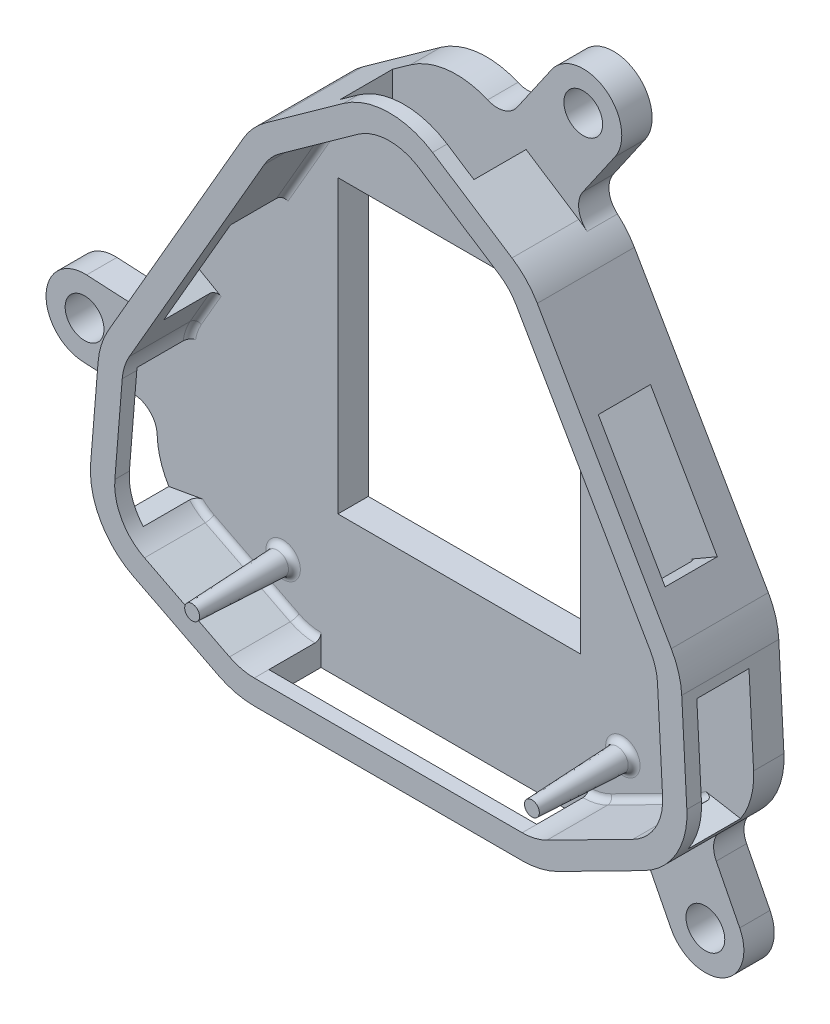
SolidWorks part; units mm, degrees
ref_plane "Front" through (0, 0, 0) normal (0, 0, 1) x (1, 0, 0)
ref_plane "Top" through (0, 0, 0) normal (0, 1, 0) x (1, 0, 0)
ref_plane "Right" through (0, 0, 0) normal (1, 0, 0) x (0, 0, -1)
sketch "Model" plane through (0, 0, 0) normal (0, 0, 1) x (1, 0, 0)
  line L0 (36.2734, 12.0044) -> (37.9734, 12.0044)
  line L1 (37.9734, 12.0044) -> (37.9734, 10.3044)
  line L2 (37.9734, 10.3044) -> (36.2734, 10.3044)
  line L3 (36.2734, 10.3044) -> (36.2734, 12.0044)
  line L4 (21.2021, 39.0514) -> (32.2167, 39.0514)
  line L5 (21.2021, 31.2458) -> (21.2021, 39.0514)
  line L6 (21.2021, 31.2458) -> (32.2167, 31.2458)
  line L7 (32.2167, 31.2458) -> (32.2167, 39.0514)
  line L8 (21.2021, 31.2458) -> (21.2021, 39.0514)
  line L9 (21.2021, 39.0514) -> (32.2167, 39.0514)
  line L10 (32.2167, 39.0514) -> (32.2167, 31.2458)
  line L11 (32.2167, 31.2458) -> (21.2021, 31.2458)
  line L12 (38.8861, 6.1621) -> (46.5731, 4.8066)
  line L13 (38.8861, 6.1621) -> (40.7988, 17.0093)
  line L14 (40.7988, 17.0093) -> (48.4858, 15.6539)
  line L15 (46.5731, 4.8066) -> (48.4858, 15.6539)
  line L16 (40.7988, 17.0093) -> (48.4858, 15.6539)
  line L17 (48.4858, 15.6539) -> (46.5731, 4.8066)
  line L18 (46.5731, 4.8066) -> (38.8861, 6.1621)
  line L19 (38.8861, 6.1621) -> (40.7988, 17.0093)
  line L20 (39.5023, 17.0656) -> (46.2621, 20.9684)
  line L21 (33.995, 26.6045) -> (39.5023, 17.0656)
  line L22 (33.995, 26.6045) -> (40.7548, 30.5073)
  line L23 (40.7548, 30.5073) -> (46.2621, 20.9684)
  line L24 (33.995, 26.6045) -> (40.7548, 30.5073)
  line L25 (40.7548, 30.5073) -> (46.2621, 20.9684)
  line L26 (46.2621, 20.9684) -> (39.5023, 17.0656)
  line L27 (39.5023, 17.0656) -> (33.995, 26.6045)
  line L28 (15.1061, 0.2754) -> (26.1207, 0.2754)
  line L29 (26.1207, 0.2754) -> (26.1207, 8.081)
  line L30 (15.1061, 8.081) -> (26.1207, 8.081)
  line L31 (15.1061, 0.2754) -> (15.1061, 8.081)
  line L32 (26.1207, 8.081) -> (26.1207, 0.2754)
  line L33 (26.1207, 0.2754) -> (15.1061, 0.2754)
  line L34 (15.1061, 0.2754) -> (15.1061, 8.081)
  line L35 (15.1061, 8.081) -> (26.1207, 8.081)
  line L36 (4.3045, 15.8277) -> (11.9916, 17.1831)
  line L37 (11.9916, 17.1831) -> (13.9042, 6.3359)
  line L38 (6.2172, 4.9804) -> (13.9042, 6.3359)
  line L39 (4.3045, 15.8277) -> (6.2172, 4.9804)
  line L40 (13.9042, 6.3359) -> (6.2172, 4.9804)
  line L41 (6.2172, 4.9804) -> (4.3045, 15.8277)
  line L42 (4.3045, 15.8277) -> (11.9916, 17.1831)
  line L43 (11.9916, 17.1831) -> (13.9042, 6.3359)
  line L44 (26.5601, 0.2754) -> (37.5747, 0.2754)
  line L45 (37.5747, 0.2754) -> (37.5747, 8.081)
  line L46 (26.5601, 8.081) -> (37.5747, 8.081)
  line L47 (26.5601, 0.2754) -> (26.5601, 8.081)
  line L48 (37.5747, 8.081) -> (37.5747, 0.2754)
  line L49 (37.5747, 0.2754) -> (26.5601, 0.2754)
  line L50 (26.5601, 0.2754) -> (26.5601, 8.081)
  line L51 (26.5601, 8.081) -> (37.5747, 8.081)
  line L52 (12.156, 29.8723) -> (18.9159, 25.9695)
  line L53 (13.4086, 16.4306) -> (18.9159, 25.9695)
  line L54 (6.6488, 20.3334) -> (13.4086, 16.4306)
  line L55 (6.6488, 20.3334) -> (12.156, 29.8723)
  line L56 (13.4086, 16.4306) -> (6.6487, 20.3334)
  line L57 (6.6487, 20.3334) -> (12.156, 29.8723)
  line L58 (12.156, 29.8723) -> (18.9159, 25.9695)
  line L59 (18.9159, 25.9695) -> (13.4086, 16.4306)
  line L60 (26.6632, 0.1484) -> (37.6778, 0.1484)
  line L61 (26.6632, 0.1484) -> (26.6632, 7.954)
  line L62 (26.6632, 7.954) -> (37.6778, 7.954)
  line L63 (37.6778, 0.1484) -> (37.6778, 7.954)
  line L64 (26.6632, 7.954) -> (26.6632, 0.1484)
  line L65 (26.6632, 0.1484) -> (37.6778, 0.1484)
  line L66 (37.6778, 0.1484) -> (37.6778, 7.954)
  line L67 (37.6778, 7.954) -> (26.6632, 7.954)
  line L68 (26.1207, 0.1483) -> (26.1207, 7.954)
  line L69 (15.1062, 7.954) -> (26.1207, 7.954)
  line L70 (15.1062, 0.1483) -> (15.1062, 7.954)
  line L71 (15.1062, 0.1483) -> (26.1207, 0.1483)
  line L72 (15.1061, 7.954) -> (15.1061, 0.1484)
  line L73 (15.1061, 0.1484) -> (26.1207, 0.1484)
  line L74 (26.1207, 0.1484) -> (26.1207, 7.954)
  line L75 (26.1207, 7.954) -> (15.1061, 7.954)
  line L76 (33.0594, 32.3634) -> (33.0594, 33.8874)
  line L77 (33.0594, 33.8874) -> (34.5834, 33.8874)
  line L78 (34.5834, 33.8874) -> (34.5834, 32.3634)
  line L79 (34.5834, 32.3634) -> (33.0594, 32.3634)
  line L80 (18.2094, 12.0434) -> (18.2094, 13.5674)
  line L81 (18.2094, 13.5674) -> (19.7334, 13.5674)
  line L82 (19.7334, 13.5674) -> (19.7334, 12.0434)
  line L83 (19.7334, 12.0434) -> (18.2094, 12.0434)
  line L84 (6.4942, 4.2177) -> (13.4987, 0.6545)
  line L85 (5.453, 17.2714) -> (16.5709, 36.5281)
  line L86 (4.321, 8.1074) -> (4.9303, 15.5958)
  line L87 (17.7062, 37.7804) -> (24.1332, 42.3823)
  line L88 (15.3123, 0.2198) -> (37.3945, 0.2198)
  line L89 (28.6426, 42.4833) -> (35.1901, 38.2252)
  line L90 (39.2081, 0.6545) -> (46.2848, 4.2545)
  line L91 (48.0448, 15.9602) -> (48.4656, 8.0316)
  line L92 (36.4735, 36.8719) -> (47.5146, 17.7482)
  circle A0 centre (26.7094, 25.3784) radius 1.4
  circle A1 centre (26.7094, 17.3784) radius 1.4
  circle A2 centre (37.1234, 18.7744) radius 0.85
  circle A3 centre (37.1234, 16.2344) radius 0.85
  circle A4 centre (37.1234, 13.6944) radius 0.85
  circle A5 centre (37.1234, 8.6144) radius 0.85
  circle A6 centre (21.2021, 39.0514) radius 0.0381
  circle A7 centre (32.2167, 39.0514) radius 0.0381
  circle A8 centre (21.2021, 31.2458) radius 0.0381
  circle A9 centre (21.2021, 39.0514) radius 0.0381
  circle A10 centre (21.2021, 31.2458) radius 0.0381
  circle A11 centre (32.2167, 31.2458) radius 0.0381
  circle A12 centre (32.2167, 31.2458) radius 0.0381
  circle A13 centre (32.2167, 39.0514) radius 0.0381
  circle A14 centre (38.8861, 6.1621) radius 0.0381
  circle A15 centre (46.5731, 4.8066) radius 0.0381
  circle A16 centre (38.8861, 6.1621) radius 0.0381
  circle A17 centre (40.7988, 17.0093) radius 0.0381
  circle A18 centre (40.7988, 17.0093) radius 0.0381
  circle A19 centre (48.4858, 15.6539) radius 0.0381
  circle A20 centre (46.5731, 4.8066) radius 0.0381
  circle A21 centre (48.4858, 15.6539) radius 0.0381
  circle A22 centre (39.5023, 17.0656) radius 0.0381
  circle A23 centre (46.2621, 20.9684) radius 0.0381
  circle A24 centre (33.995, 26.6045) radius 0.0381
  circle A25 centre (39.5023, 17.0656) radius 0.0381
  circle A26 centre (33.995, 26.6045) radius 0.0381
  circle A27 centre (40.7548, 30.5073) radius 0.0381
  circle A28 centre (40.7548, 30.5073) radius 0.0381
  circle A29 centre (46.2621, 20.9684) radius 0.0381
  circle A30 centre (15.1061, 0.2754) radius 0.0381
  circle A31 centre (26.1207, 0.2754) radius 0.0381
  circle A32 centre (26.1207, 0.2754) radius 0.0381
  circle A33 centre (26.1207, 8.081) radius 0.0381
  circle A34 centre (15.1061, 8.081) radius 0.0381
  circle A35 centre (26.1207, 8.081) radius 0.0381
  circle A36 centre (15.1061, 0.2754) radius 0.0381
  circle A37 centre (15.1061, 8.081) radius 0.0381
  circle A38 centre (4.3045, 15.8277) radius 0.0381
  circle A39 centre (11.9916, 17.1831) radius 0.0381
  circle A40 centre (11.9916, 17.1831) radius 0.0381
  circle A41 centre (13.9042, 6.3359) radius 0.0381
  circle A42 centre (6.2172, 4.9804) radius 0.0381
  circle A43 centre (13.9042, 6.3359) radius 0.0381
  circle A44 centre (4.3045, 15.8277) radius 0.0381
  circle A45 centre (6.2172, 4.9804) radius 0.0381
  circle A46 centre (26.5601, 0.2754) radius 0.0381
  circle A47 centre (37.5747, 0.2754) radius 0.0381
  circle A48 centre (37.5747, 0.2754) radius 0.0381
  circle A49 centre (37.5747, 8.081) radius 0.0381
  circle A50 centre (26.5601, 8.081) radius 0.0381
  circle A51 centre (37.5747, 8.081) radius 0.0381
  circle A52 centre (26.5601, 0.2754) radius 0.0381
  circle A53 centre (26.5601, 8.081) radius 0.0381
  circle A54 centre (12.156, 29.8723) radius 0.0381
  circle A55 centre (18.9159, 25.9695) radius 0.0381
  circle A56 centre (13.4086, 16.4306) radius 0.0381
  circle A57 centre (18.9159, 25.9695) radius 0.0381
  circle A58 centre (6.6488, 20.3334) radius 0.0381
  circle A59 centre (13.4086, 16.4306) radius 0.0381
  circle A60 centre (6.6488, 20.3334) radius 0.0381
  circle A61 centre (12.156, 29.8723) radius 0.0381
  circle A62 centre (26.6632, 0.1484) radius 0.0381
  circle A63 centre (37.6778, 0.1484) radius 0.0381
  circle A64 centre (26.6632, 0.1484) radius 0.0381
  circle A65 centre (26.6632, 7.954) radius 0.0381
  circle A66 centre (26.6632, 7.954) radius 0.0381
  circle A67 centre (37.6778, 7.954) radius 0.0381
  circle A68 centre (37.6778, 0.1484) radius 0.0381
  circle A69 centre (37.6778, 7.954) radius 0.0381
  circle A70 centre (26.1207, 0.1483) radius 0.0381
  circle A71 centre (26.1207, 7.954) radius 0.0381
  circle A72 centre (15.1062, 7.954) radius 0.0381
  circle A73 centre (26.1207, 7.954) radius 0.0381
  circle A74 centre (15.1062, 0.1483) radius 0.0381
  circle A75 centre (15.1062, 7.954) radius 0.0381
  circle A76 centre (15.1062, 0.1483) radius 0.0381
  circle A77 centre (26.1207, 0.1483) radius 0.0381
  circle A78 centre (18.9714, 22.9654) radius 0.762
  circle A79 centre (18.9714, 25.5054) radius 0.762
  circle A80 centre (18.9714, 28.0454) radius 0.762
  circle A81 centre (18.9714, 30.5854) radius 0.762
  circle A82 centre (18.9714, 33.1254) radius 0.762
  circle A83 centre (33.8214, 10.2654) radius 0.762
  circle A84 centre (33.8214, 12.8054) radius 0.762
  circle A85 centre (33.8214, 15.3454) radius 0.762
  circle A86 centre (33.8214, 17.8854) radius 0.762
  circle A87 centre (33.8214, 20.4254) radius 0.762
  circle A88 centre (33.8214, 22.9654) radius 0.762
  circle A89 centre (33.8214, 25.5054) radius 0.762
  circle A90 centre (33.8214, 28.0454) radius 0.762
  circle A91 centre (33.8214, 30.5854) radius 0.762
  circle A92 centre (18.9714, 20.4254) radius 0.762
  circle A93 centre (18.9714, 17.8854) radius 0.762
  circle A94 centre (18.9714, 15.3454) radius 0.762
  circle A95 centre (18.9714, 10.2654) radius 0.762
  circle A96 centre (6.4942, 4.2177) radius 0.0032
  circle A97 centre (13.4987, 0.6545) radius 0.0032
  circle A98 centre (5.453, 17.2714) radius 0.0032
  circle A99 centre (16.5709, 36.5281) radius 0.0032
  circle A100 centre (4.321, 8.1074) radius 0.0032
  circle A101 centre (4.9303, 15.5958) radius 0.0032
  circle A102 centre (17.7062, 37.7804) radius 0.0032
  circle A103 centre (24.1332, 42.3823) radius 0.0032
  circle A104 centre (15.3123, 0.2198) radius 0.0032
  circle A105 centre (37.3945, 0.2198) radius 0.0032
  circle A106 centre (28.6426, 42.4833) radius 0.0032
  circle A107 centre (35.1901, 38.2252) radius 0.0032
  circle A108 centre (39.2081, 0.6545) radius 0.0032
  circle A109 centre (46.2848, 4.2545) radius 0.0032
  circle A110 centre (48.0448, 15.9602) radius 0.0032
  circle A111 centre (48.4656, 8.0316) radius 0.0032
  circle A112 centre (36.4735, 36.8719) radius 0.0032
  circle A113 centre (47.5146, 17.7482) radius 0.0032
  arc A114 (4.321, 8.1074) -> (6.4942, 4.2177) centre (8.3078, 7.783) ccw
  circle A115 centre (6.4942, 4.2177) radius 0.0032
  circle A116 centre (4.321, 8.1074) radius 0.0032
  arc A117 (28.6426, 42.4833) -> (24.1332, 42.3823) centre (26.4619, 39.13) ccw
  circle A118 centre (24.1332, 42.3823) radius 0.0032
  circle A119 centre (28.6426, 42.4833) radius 0.0032
  arc A120 (5.453, 17.2714) -> (4.9303, 15.5958) centre (8.9171, 15.2714) ccw
  circle A121 centre (4.9303, 15.5958) radius 0.0032
  circle A122 centre (5.453, 17.2714) radius 0.0032
  arc A123 (17.7062, 37.7804) -> (16.5709, 36.5281) centre (20.035, 34.5282) ccw
  circle A124 centre (16.5709, 36.5281) radius 0.0032
  circle A125 centre (17.7063, 37.7804) radius 0.0032
  arc A126 (36.4735, 36.8719) -> (35.1901, 38.2252) centre (33.0094, 34.8719) ccw
  circle A127 centre (35.1901, 38.2252) radius 0.0032
  circle A128 centre (36.4735, 36.8719) radius 0.0032
  arc A129 (37.3945, 0.2198) -> (39.2081, 0.6545) centre (37.3946, 4.2198) ccw
  circle A130 centre (39.2081, 0.6545) radius 0.0032
  circle A131 centre (37.3945, 0.2197) radius 0.0032
  arc A132 (46.2848, 4.2545) -> (48.4656, 8.0316) centre (44.4712, 7.8197) ccw
  circle A133 centre (48.4656, 8.0316) radius 0.0032
  circle A134 centre (46.2848, 4.2544) radius 0.0032
  arc A135 (48.0448, 15.9602) -> (47.5146, 17.7482) centre (44.0504, 15.7483) ccw
  circle A136 centre (47.5146, 17.7482) radius 0.0032
  circle A137 centre (48.0448, 15.9602) radius 0.0032
  arc A138 (13.4987, 0.6545) -> (15.3123, 0.2198) centre (15.3123, 4.2198) ccw
  circle A139 centre (15.3124, 0.2197) radius 0.0032
  circle A140 centre (13.4987, 0.6545) radius 0.0032
  circle A141 centre (40.1914, 3.8534) radius 1.5
  circle A142 centre (26.4554, 40.8724) radius 1.5
  circle A143 centre (12.1915, 3.8534) radius 1.5
sketch "Sketch4" plane through (0, 0, 0) normal (0, 0, 1) x (1, 0, 0)
  line L0 (26.7094, 25.3784) -> (26.7094, 17.3784) construction
  line L1 (36.7094, 9.3784) -> (16.7094, 9.3784)
  line L2 (36.7094, 9.3784) -> (36.7094, 33.3784)
  line L3 (36.7094, 33.3784) -> (16.7094, 33.3784)
  line L4 (16.7094, 9.3784) -> (16.7094, 33.3784)
  line L5 (36.7094, 9.3784) -> (16.7094, 33.3784) construction
  line L6 (36.7094, 33.3784) -> (16.7094, 9.3784) construction
  line L89 (14.4058, 37.7781) -> (3.2879, 18.5214)
  line L90 (2.4385, 15.7986) -> (1.8292, 8.3101)
  line L91 (5.3607, 1.9895) -> (12.3653, -1.5738)
  line L92 (15.3124, -2.2802) -> (37.3945, -2.2802)
  line L93 (40.3416, -1.5738) -> (47.4183, 2.0262)
  line L94 (50.9621, 8.1641) -> (50.5413, 16.0927)
  line L95 (49.6796, 18.9982) -> (38.6386, 38.1219)
  line L96 (36.5531, 40.321) -> (30.0056, 44.5791)
  line L97 (22.6777, 44.4149) -> (16.2508, 39.8131)
  line L98 (16.1379, 36.7781) -> (5.02, 17.5214)
  line L99 (4.4319, 15.6364) -> (3.8226, 8.1479)
  line L100 (6.2675, 3.7721) -> (13.272, 0.2089)
  line L101 (15.3124, -0.2802) -> (37.3945, -0.2802)
  line L102 (39.4348, 0.2089) -> (46.5115, 3.8088)
  line L103 (48.9649, 8.0581) -> (48.5441, 15.9867)
  line L104 (47.9476, 17.9982) -> (36.9065, 37.1219)
  line L105 (35.4627, 38.6443) -> (28.9152, 42.9024)
  line L106 (23.8421, 42.7888) -> (17.4152, 38.1869)
  line L107 (16.1379, 36.7781) -> (5.02, 17.5214)
  line L108 (4.4319, 15.6364) -> (3.8226, 8.1479)
  line L109 (6.2675, 3.7721) -> (13.272, 0.2089)
  line L110 (15.3124, -0.2802) -> (37.3945, -0.2802)
  line L111 (39.4348, 0.2089) -> (46.5115, 3.8088)
  line L112 (48.9649, 8.0581) -> (48.5441, 15.9867)
  line L113 (47.9476, 17.9982) -> (36.9065, 37.1219)
  line L114 (35.4627, 38.6443) -> (28.9152, 42.9024)
  line L115 (23.8421, 42.7888) -> (17.4152, 38.1869)
  circle A5 centre (12.1915, 3.8534) radius 1.05
  circle A6 centre (12.1915, 3.8534) radius 1.05
  circle A7 centre (26.3789, 18.2477) radius 27.3825 construction
  circle A8 centre (40.1914, 3.8534) radius 1.05
  circle A9 centre (40.1914, 3.8534) radius 1.05
  arc A81 (3.2879, 18.5214) -> (2.4385, 15.7986) centre (8.9171, 15.2714) ccw
  arc A82 (1.8292, 8.3101) -> (5.3607, 1.9895) centre (8.3078, 7.783) ccw
  arc A83 (12.3653, -1.5738) -> (15.3124, -2.2802) centre (15.3123, 4.2198) ccw
  arc A84 (37.3945, -2.2802) -> (40.3416, -1.5738) centre (37.3946, 4.2198) ccw
  arc A85 (47.4183, 2.0262) -> (50.9621, 8.1641) centre (44.4712, 7.8197) ccw
  arc A86 (50.5413, 16.0927) -> (49.6796, 18.9982) centre (44.0504, 15.7483) ccw
  arc A87 (38.6386, 38.1219) -> (36.5531, 40.321) centre (33.0094, 34.8719) ccw
  arc A88 (30.0056, 44.5791) -> (22.6777, 44.4149) centre (26.4619, 39.13) ccw
  arc A89 (16.2508, 39.8131) -> (14.4058, 37.7781) centre (20.035, 34.5282) ccw
  arc A90 (17.4152, 38.1869) -> (16.1379, 36.7781) centre (20.035, 34.5282) ccw
  arc A91 (5.02, 17.5214) -> (4.4319, 15.6364) centre (8.9171, 15.2714) ccw
  arc A92 (3.8226, 8.1479) -> (6.2675, 3.7721) centre (8.3078, 7.783) ccw
  arc A93 (13.272, 0.2089) -> (15.3124, -0.2802) centre (15.3123, 4.2198) ccw
  arc A94 (37.3945, -0.2802) -> (39.4348, 0.2089) centre (37.3946, 4.2198) ccw
  arc A95 (46.5115, 3.8088) -> (48.9649, 8.0581) centre (44.4712, 7.8197) ccw
  arc A96 (48.5441, 15.9867) -> (47.9476, 17.9982) centre (44.0504, 15.7483) ccw
  arc A97 (36.9065, 37.1219) -> (35.4627, 38.6443) centre (33.0094, 34.8719) ccw
  arc A98 (28.9152, 42.9024) -> (23.8421, 42.7888) centre (26.4619, 39.13) ccw
  arc A99 (17.4152, 38.1869) -> (16.1379, 36.7781) centre (20.035, 34.5282) ccw
  arc A100 (5.02, 17.5214) -> (4.4319, 15.6364) centre (8.9171, 15.2714) ccw
  arc A101 (3.8226, 8.1479) -> (6.2675, 3.7721) centre (8.3078, 7.783) ccw
  arc A102 (13.272, 0.2089) -> (15.3124, -0.2802) centre (15.3123, 4.2198) ccw
  arc A103 (37.3945, -0.2802) -> (39.4348, 0.2089) centre (37.3946, 4.2198) ccw
  arc A104 (46.5115, 3.8088) -> (48.9649, 8.0581) centre (44.4712, 7.8197) ccw
  arc A105 (48.5441, 15.9867) -> (47.9476, 17.9982) centre (44.0504, 15.7483) ccw
  arc A106 (36.9065, 37.1219) -> (35.4627, 38.6443) centre (33.0094, 34.8719) ccw
  arc A107 (28.9152, 42.9024) -> (23.8421, 42.7888) centre (26.4619, 39.13) ccw
  point P27 (26.7094, 21.3784)
  dimension "D4" = 24
  dimension "D3" = 20
  dimension "D1" = 0.5
  dimension "D2" = 2
  dimension "D5" = 0.45
  dimension "D6" = 0.45
extrude "Boss-Extrude1" add sketch "Sketch4" along normal blind 2.5 contours L114 A107 L115 A99 L107 A100 L108 A101 L109 A102 L110 A103 L111 A104 L112 A105 L113 A106 | L97 A89 L89 A81 L90 A82 L91 A83 L92 A84 L93 A85 L94 A86 L95 A87 L96 A88 A107 L114 A106 L113 A105 L112 A104 L111 A103 L110 A102 L109 A101 L108 A100 L107 A99 L115 | A6 | A9 region at (15.7281, 38.4331, 0) region at (17.1679, 37.1277, 0) region at (12.1915, 3.8534, 0) region at (40.1914, 3.8534, 0)
extrude "Boss-Extrude3" add sketch "Sketch4<4>" along normal blind 8 contours L97 A89 L89 A81 L90 A82 L91 A83 L92 A84 L93 A85 L94 A86 L95 A87 L96 A88 A107 L114 A106 L113 A105 L112 A104 L111 A103 L110 A102 L109 A101 L108 A100 L107 A99 L115 region at (15.7281, 38.4331, 0)
sketch "Sketch4<4>" plane through (0, 0, 0) normal (0, 0, 1) x (1, 0, 0) same geometry as "Sketch4"
extrude "Boss-Extrude4" add sketch "Sketch4<5>" along normal blind 10 draft 2.5 separate body contours A6 | A9 region at (12.1915, 3.8534, 0) region at (40.1914, 3.8534, 0)
sketch "Sketch4<5>" plane through (0, 0, 0) normal (0, 0, 1) x (1, 0, 0) same geometry as "Sketch4"
combine bodies "Combine1" operation type add bodies to combine 108 107 106
sketch "Sketch5" plane through (0, -2.2802, 0) normal (0, -1, 0) x (1, 0, 0)
  line L0 (26.6632, 0) -> (37.6778, 0) construction
  line L1 (15.1062, 0) -> (26.1207, 0) construction
  line L2 (26.6632, 0) -> (37.6778, 0) construction
  line L3 (15.1062, 0) -> (26.1207, 0) construction
  line L4 (37.3945, 2.5) -> (15.3124, 2.5) construction
  line L5 (37.6778, 2.5) -> (15.1062, 2.5)
  line L7 (15.1062, 2.5) -> (37.6778, 2.5)
  line L8 (15.1062, 2.5) -> (15.1062, 6.8)
  line L9 (15.1062, 6.8) -> (37.6778, 6.8)
  line L10 (37.6778, 2.5) -> (37.6778, 6.8)
  line M8 (37.3945, 0) -> (37.3945, 8)
  line M10 (15.3124, 8) -> (15.3124, 0)
  dimension "D1" = 4.3
extrude "Cut-Extrude1" cut sketch "Sketch5" against normal up to surface (2 mm away) contours L9 L5 M10 M8 region at (26.3534, -2.2802, 4.65) up to face at (26.3534, -0.2802, 5.25)
sketch "Sketch6" plane through (-5.5541, 3.2066, 0) normal (-0.866, 0.5, 0) x (0, 0, 1)
  line L0 (0, 20.9336) -> (0, 31.9482) construction
  line L1 (0, 20.9336) -> (0, 31.9482) construction
  line L2 (2.5, 17.684) -> (2.5, 39.9197) construction
  line L3 (2.5, 20.9336) -> (2.5, 31.9482)
  line L4 (2.5, 31.9482) -> (6.8, 31.9482)
  line L5 (6.8, 31.9482) -> (6.8, 20.9336)
  line L6 (6.8, 20.9336) -> (2.5, 20.9336)
  dimension "D1" = 4.3
extrude "Cut-Extrude2" cut sketch "Sketch6" against normal up to surface (2 mm away) up to face at (10.5789, 27.1498, 5.25)
sketch "Sketch7" plane through (45.4862, 26.2615, 0) normal (0.866, 0.5, 0) x (0, 0, -1)
  line L0 (-2.5, 13.6953) -> (-2.5, -8.3869) construction
  line L1 (0, 6.0427) -> (0, -4.9719) construction
  line L2 (-2.5, 6.0427) -> (-2.5, -4.9719)
  line L3 (0, 6.0427) -> (0, -4.9719) construction
  line L4 (-2.5, -4.9719) -> (-6.8, -4.9719)
  line L5 (-6.8, -4.9719) -> (-6.8, 6.0427)
  line L6 (-6.8, 6.0427) -> (-2.5, 6.0427)
  dimension "D1" = 4.3
extrude "Cut-Extrude3" cut sketch "Sketch7" against normal up to surface (2 mm away) up to face at (42.427, 27.5601, 5.25)
ref_plane "Plane1" through (0, 39.0514, 0) normal (0, 1, 0) x (1, 0, 0)
sketch "Sketch8" plane through (0, 39.0514, 0) normal (0, 1, 0) x (1, 0, 0)
  line L0 (21.2021, 0) -> (32.2167, 0) construction
  line L1 (37.3945, -2.5) -> (15.3124, -2.5) construction
  line L2 (21.2021, 0) -> (32.2167, 0) construction
  line L3 (32.2167, -2.5) -> (21.2021, -2.5)
  line L4 (21.2021, -2.5) -> (21.2021, -6.8)
  line L7 (32.2167, -6.8) -> (32.2167, -2.5)
  line L8 (21.2021, -6.8) -> (32.2167, -6.8)
  dimension "D1" = 4.3
extrude "Cut-Extrude5" cut sketch "Sketch8" along normal blind 7
ref_plane "Plane2" through (6.2172, 4.9804, 0) normal (0.9848, 0.1737, 0) x (0, 0, -1)
sketch "Sketch9" plane through (6.2172, 4.9804, 0) normal (0.9848, 0.1737, 0) x (0, 0, -1)
  line L0 (-2.5, 8.7825) -> (-2.5, 5.5735) construction
  line L1 (0, 11.0146) -> (0, 0) construction
  line L2 (-2.5, 11.0146) -> (-2.5, 0)
  line L3 (0, 11.0146) -> (0, 0)
  line L4 (-2.5, 0) -> (-6.8, 0)
  line L5 (-6.8, 0) -> (-6.8, 11.0146)
  line L6 (-6.8, 11.0146) -> (-2.5, 11.0146)
  dimension "D1" = 4.3
extrude "Cut-Extrude6" cut sketch "Sketch9" against normal blind 7 and the other way blind 7 contours L6 L5 L4 L2 region at (5.2609, 10.4041, 4.65)
ref_plane "Plane3" through (40.7988, 17.0093, 0) normal (0.9848, -0.1736, 0) x (0, 0, -1)
sketch "Sketch10" plane through (40.7988, 17.0093, 0) normal (0.9848, -0.1736, 0) x (0, 0, -1)
  line L0 (-2.5, -5.7085) -> (-2.5, -2.6548) construction
  line L1 (0, -11.0146) -> (0, 0) construction
  line L2 (-2.5, -11.0146) -> (-2.5, 0)
  line L3 (0, -11.0146) -> (0, 0)
  line L4 (-2.5, 0) -> (-6.8, 0)
  line L5 (-6.8, 0) -> (-6.8, -11.0146)
  line L6 (-6.8, -11.0146) -> (-2.5, -11.0146)
  dimension "D1" = 4.3
extrude "Cut-Extrude7" cut sketch "Sketch10" along normal through all contours L5 L6 L2 L4 region at (39.8424, 11.5857, 4.65)
fillet "Fillet1" radius 0.5 19 edges at (33.8397, 39.6998, 2.5) (36.2746, 37.9684, 2.5) (48.5533, 15.8135, 2.5) (48.3647, 17.0277, 2.5) (47.1046, 4.1706, 2.5) (38.4436, -0.1563, 2.5) (14.2633, -0.1563, 2.5) (5.5753, 4.2075, 2.5) (4.6552, 16.7157, 2.5) (14.145, 33.3264, 2.5) (16.7012, 37.5508, 2.5) (38.8196, 33.8083, 2.5) (47.0938, 19.4769, 2.5) (42.9732, 2.0088, 2.5) (9.7698, 1.9905, 2.5) (5.8324, 18.9285, 2.5) (19.3086, 39.5427, 2.5) (37.3945, -0.2802, 2.5) (15.3124, -0.2802, 2.5)
sketch "Sketch11" plane through (0, 0, 0) normal (0, 0, -1) x (-1, 0, 0)
  line L0 (4.0046, 16.0801) -> (-2.4626, 15.737) construction
  line L1 (-2.0619, 9.3993) -> (4.341, 9.7391) construction
  line L2 (-44.1594, -6.4916) -> (-41.2167, -0.707) construction
  line L3 (-46.9089, 2.1084) -> (-49.8191, -3.6125) construction
  line L4 (-39.5369, 46.2793) -> (-35.805, 40.8801) construction
  line L5 (-30.644, 44.5812) -> (-34.3132, 49.8899) construction
  line L6 (4.0046, 16.0801) -> (-2.4336, 15.7385)
  line L7 (-1.9184, 9.4069) -> (4.341, 9.7391)
  line L8 (-44.1594, -6.4916) -> (-41.3871, -1.0419)
  line L9 (-47.0469, 1.8372) -> (-49.8191, -3.6125)
  line L10 (-39.5369, 46.2793) -> (-35.7704, 40.83)
  line L11 (-30.445, 44.2933) -> (-34.3132, 49.8899)
  line L12 (-2.4385, 15.7986) -> (-1.8292, 8.3101) construction
  line L13 (-1.9184, 9.4069) -> (-2.4336, 15.7385)
  line L14 (-40.3416, -1.5738) -> (-47.4183, 2.0262) construction
  line L15 (-47.0469, 1.8372) -> (-41.3871, -1.0419)
  line L16 (-36.5531, 40.321) -> (-30.0056, 44.5791) construction
  line L17 (-35.7704, 40.83) -> (-30.445, 44.2933)
  arc A0 (4.341, 9.7391) -> (4.0046, 16.0801) centre (4.1728, 12.9096) ccw construction
  arc A1 (-49.8191, -3.6125) -> (-44.1594, -6.4916) centre (-46.9892, -5.0521) ccw construction
  arc A2 (-34.3132, 49.8899) -> (-39.5369, 46.2793) centre (-36.9251, 48.0846) ccw construction
  arc A3 (4.341, 9.7391) -> (4.0046, 16.0801) centre (4.1728, 12.9096) ccw
  arc A4 (-49.8191, -3.6125) -> (-44.1594, -6.4916) centre (-46.9892, -5.0521) ccw
  arc A5 (-34.3132, 49.8899) -> (-39.5369, 46.2793) centre (-36.9251, 48.0846) ccw
  circle A6 centre (4.1728, 12.9096) radius 1.6 construction
  circle A7 centre (-46.9892, -5.0521) radius 1.6 construction
  circle A8 centre (-36.9251, 48.0846) radius 1.6 construction
  circle A9 centre (4.1728, 12.9096) radius 1.6
  circle A10 centre (-46.9892, -5.0521) radius 1.6
  circle A11 centre (-36.9251, 48.0846) radius 1.6
extrude "Boss-Extrude5" add sketch "Sketch11" against normal up to surface (2.5 mm away) up to face at (26.9536, 19.7187, 2.5)
fillet "Fillet2" radius 2 6 edges at (41.3871, -1.0419, 1.25) (47.0469, 1.8372, 1.25) (35.7704, 40.83, 1.25) (30.445, 44.2933, 1.25) (2.4336, 15.7385, 1.25) (1.9184, 9.4069, 1.25)
fillet "Fillet3" radius 0.5 2 edges at (41.1323, 3.8534, 2.5) (13.1323, 3.8534, 2.5)
